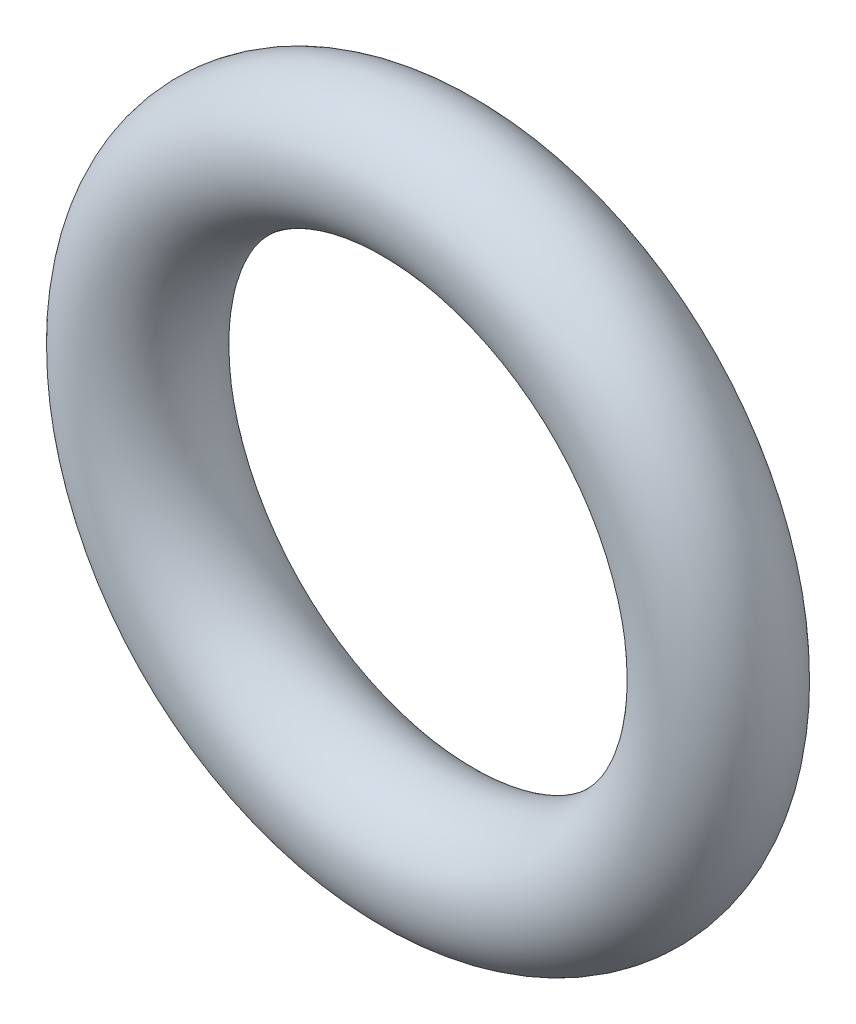
SolidWorks part; units mm, degrees
ref_plane "Top" through (0, 0, 0) normal (0, 0, 1) x (1, 0, 0)
ref_plane "Front" through (0, 0, 0) normal (0, 1, 0) x (1, 0, 0)
ref_plane "Right" through (0, 0, 0) normal (1, 0, 0) x (0, 0, -1)
sketch "O-Ring Sketch" plane through (0, 0, 0) normal (0, 1, 0) x (1, 0, 0)
  line L0 (0, 0) -> (0, 0.5) construction
  line L1 (1.75, -0.5) -> (2.75, -0.5) construction
  line L2 (1.75, -0.5) -> (1.75, 0.5) construction
  line L3 (1.75, 0.5) -> (2.75, 0.5) construction
  line L4 (2.75, -0.5) -> (2.75, 0.5) construction
  line L5 (2.25, 0.5) -> (2.25, -0.5) construction
  line L6 (1.75, 0) -> (2.75, 0) construction
  line L7 (-1.75, -0.5) -> (-1.75, 0.5) construction
  line L8 (-2.75, -0.5) -> (-2.75, 0.5) construction
  circle A0 centre (2.25, 0) radius 0.5
  point P275 (2.25, 0)
  dimension "Inner Diameter" = 3.5
  dimension "Outer Diameter" = 5.5
revolve "O-Ring Revolve" add sketch "O-Ring Sketch" angle 360 about L0
ref_axis "Centerline Axis" [suppressed] through (0, 0, -80.9) along (0, 0, 1)
equation "\"M2 Close Fit Hole\"= 2.2"
equation "\"M2.5 Close Fit Hole\"= 2.7"
equation "\"M3 Close Fit Hole\"= 3.2"
equation "\"M4 Close Fit Hole\"= 4.3"
equation "\"M5 Close Fit Hole\"= 5.3"
equation "\"M6 Close Fit Hole\"= 6.3"
equation "\"M7 Close Fit Hole\"= 7.4"
equation "\"M8 Close Fit Hole\"= 8.4"
equation "\"M2 Tap Hole 75%\"= 1.6"
equation "\"M3 Tap Hole 75%\"= 2.5"
equation "\"M4 Tap Hole 75%\"= 3.3"
equation "\"M5 Tap Hole 75%\"= 4.2"
equation "\"M6 Tap Hole 75%\"= 5"
equation "\"M7 Tap Hole 75%\"= 6"
equation "\"M8 Tap Hole 75%\"= 6.8"
